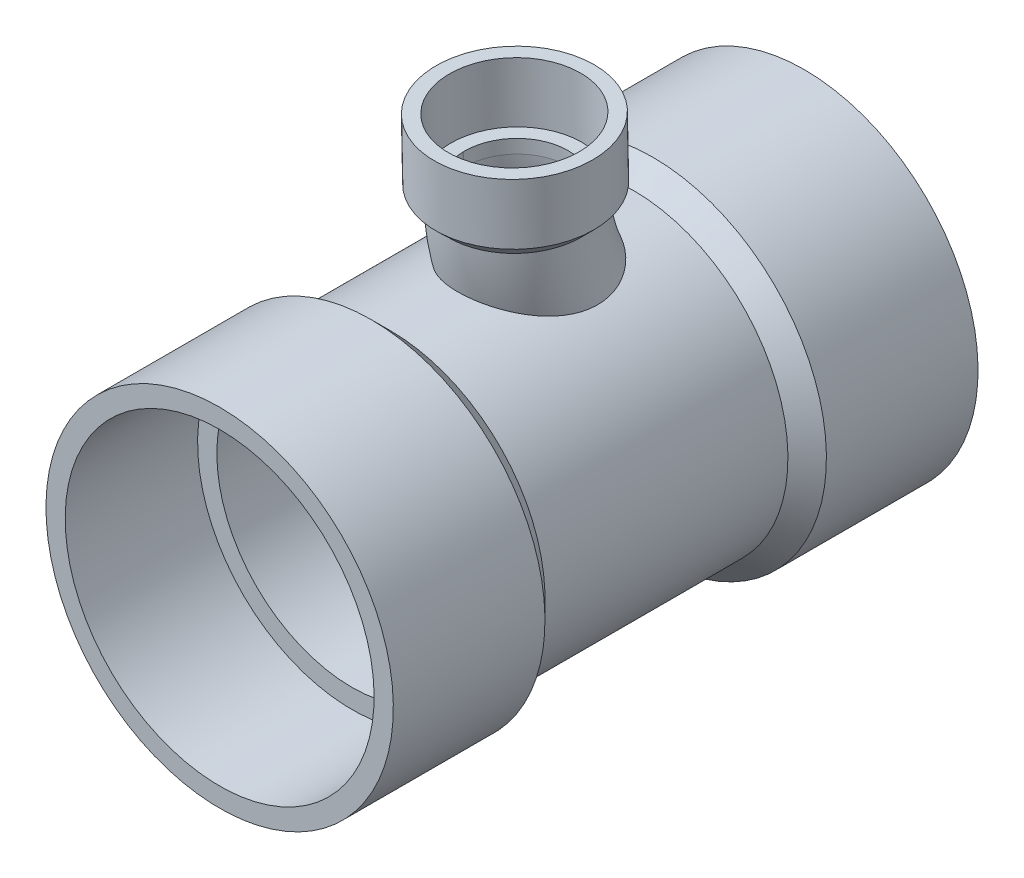
SolidWorks part; units mm, degrees
ref_plane "Front Plane" through (0, 0, 0) normal (0, 0, 1) x (1, 0, 0)
ref_plane "Top Plane" through (0, 0, 0) normal (0, 1, 0) x (1, 0, 0)
ref_plane "Right Plane" through (0, 0, 0) normal (1, 0, 0) x (0, 0, -1)
sketch "RunRoute" plane through (0, 0, 0) normal (0, 0, 1) x (1, 0, 0)
  circle A0 centre (0, 0) radius 44.45
  circle A1 centre (0, 0) radius 38.9128
  dimension "Diameter" = 88.9
  dimension "HubD" = 5.5372
sketch "Sketch2" plane through (0, 0, 0) normal (1, 0, 0) x (0, 0, -1)
  line L0 (0, 0) -> (-1.3301, 63.5) construction
  line L1 (0, 0) -> (-48.4188, 0) construction
  line L2 (0, 0) -> (43.6562, 0) construction
  arc A0 (-1.3301, 63.5) -> (43.6562, 0) centre (68.0302, 64.9529) ccw
  point P7 (43.0139, 0)
  point P8 (0, 0)
  dimension "DimensionC" = 43.6562
  dimension "DimensionB" = 92.075
  dimension "Angle" = 88.8
  dimension "DimensionA" = 63.5
ref_plane "Outlet Plane" through (0, 63.5, 1.3301) normal (0, 0.9998, 0.0209) x (1, 0, 0)
sketch "OutletRoute" plane through (0, 63.5, 1.3301) normal (0, 0.9998, 0.0209) x (1, 0, 0)
  circle A0 centre (0, 0) radius 19.05
  circle A1 centre (0, 0) radius 15.0876
  dimension "OutletHubD" = 3.9624
  dimension "OutletRoute" = 38.1
extrude "Boss-Extrude1" add sketch "RunRoute" along normal up to vertex (48.4188 mm away) and the other way up to vertex (43.6562 mm away) up to point (0, 0, 48.4188) other way up to point (0, 0, -43.6562)
sketch "Sketch6" plane through (0, 0, 0) normal (1, 0, 0) x (0, 0, -1)
  line L0 (17.7157, 63.899) -> (-20.376, 63.101) construction
  line L1 (43.6562, 44.45) -> (-48.4188, 44.45) construction
  line L2 (17.7157, 63.899) -> (17.0887, 93.8332) construction
  line L3 (-20.376, 63.101) -> (-20.9875, 92.2953) construction
  line L4 (43.6562, 44.45) -> (-48.4188, 44.45) construction
  line L6 (13.7542, 63.816) -> (-16.4144, 63.184) construction
  arc A0 (17.7157, 63.899) -> (22.0705, 44.45) centre (68.0302, 64.9529) ccw
  arc A1 (-20.376, 63.101) -> (-17.9856, 44.45) centre (68.0302, 64.9529) ccw
  arc A2 (-16.4144, 63.184) -> (-13.9067, 44.45) centre (68.0302, 64.9529) ccw
  arc A3 (13.7542, 63.816) -> (17.7628, 44.45) centre (68.0302, 64.9529) ccw
  arc A4 (-1.3301, 63.5) -> (43.6562, 0) centre (68.0302, 64.9529) ccw construction
  point P6 (0, 0)
  point P9 (0, 0)
  point P10 (24.9769, 44.45)
  point P21 (19.1248, 44.45)
  point P28 (-11.192, 44.45)
ref_plane "Plane2" through (0, 44.45, 0) normal (0, -1, 0) x (-1, 0, 0)
sweep "Sweep1" add profiles "OutletRoute" path "Sketch2"
sketch "Sketch3" plane through (0, 0, 0) normal (1, 0, 0) x (0, 0, -1)
  line L0 (43.6562, 0) -> (43.6562, -38.9128) construction
  line L1 (43.6562, -44.45) -> (81.7563, -44.45)
  line L2 (81.7563, -44.45) -> (81.7563, -49.9872)
  line L3 (81.7563, -49.9872) -> (38.1191, -49.9872)
  line L4 (38.1191, -49.9872) -> (32.5819, -44.45)
  line L5 (32.5819, -44.45) -> (32.5819, -38.9128)
  line L6 (32.5819, -38.9128) -> (43.6562, -38.9128)
  line L7 (43.6562, -38.9128) -> (43.6562, -44.45)
  line L8 (0, 0) -> (43.6562, 0) construction
  line L11 (43.6562, 0) -> (81.7562, 0) construction
  line L12 (81.7562, 0) -> (81.7563, -44.45) construction
  line L13 (-48.4188, -44.45) -> (43.6562, -44.45) construction
  line L14 (-48.4188, 0) -> (-86.5187, 0) construction
  line L15 (-86.5187, 0) -> (-86.5187, -44.45) construction
  line L16 (-86.5187, -44.45) -> (-86.5187, -49.9872)
  line L17 (-86.5187, -49.9872) -> (-42.8815, -49.9872)
  line L18 (-42.8815, -49.9872) -> (-37.3443, -44.45)
  line L19 (-37.3443, -44.45) -> (-37.3443, -38.9128)
  line L20 (-37.3443, -38.9128) -> (-48.4188, -38.9128)
  line L21 (-48.4188, -38.9128) -> (-48.4187, -44.45)
  line L22 (-48.4187, -44.45) -> (-86.5187, -44.45)
  line L25 (17.3502, 81.3449) -> (21.3118, 81.4279)
  line L26 (-1.3301, 63.5) -> (-1.6956, 80.946) construction
  line L27 (0, 0) -> (-1.3301, 63.5) construction
  line L28 (-1.6956, 80.946) -> (17.3502, 81.3449) construction
  line L29 (21.3118, 81.4279) -> (21.6805, 63.8257)
  line L30 (17.3502, 81.3449) -> (17.7157, 63.899)
  line L31 (21.6805, 63.8257) -> (17.9549, 59.9407)
  line L32 (17.9549, 59.9407) -> (13.8371, 59.8544)
  line L33 (13.8371, 59.8544) -> (13.7542, 63.816)
  line L34 (13.7542, 63.816) -> (17.7157, 63.899)
  arc A0 (17.7157, 63.899) -> (22.0705, 44.45) centre (68.0302, 64.9529) ccw construction
  point P18 (0, 0)
  dimension "HubC" = 38.1
  dimension "D1" = 5.5372
  dimension "D2" = 88.9
  dimension "D3" = 45
  dimension "D4" = 5.5372
  dimension "D5" = 45
  dimension "D6" = 5.5372
  dimension "D7" = 45
  dimension "OutletHubC" = 17.4498
  dimension "OutletHubD" = 3.9624
  dimension "D8" = 38.1
  dimension "D9" = 3.9624
extrude "Cut-Extrude1" cut sketch "RunRoute<2>" against normal through all both and the other way through all contours A1 region at (0, 0, 0)
sketch "RunRoute<2>" plane through (0, 0, 0) normal (0, 0, 1) x (1, 0, 0) same geometry as "RunRoute"
revolve "Revolve1" add sketch "Sketch3" angle 360 about L26 region at (0, 69.9322, -18.8487)
revolve "Revolve2" add sketch "Sketch3<5>" angle 360 about L14 region at (0, -46.1073, -54.5942) region at (0, -46.1073, 59.3567)
sketch "Sketch3<5>" plane through (0, 0, 0) normal (1, 0, 0) x (0, 0, -1) same geometry as "Sketch3"
ref_plane "Plane3" through (0, 0, 48.4188) normal (0, 0, 1) x (1, 0, 0)
ref_plane "Plane4" through (0, 0, -43.6562) normal (0, 0, -1) x (-1, 0, 0)
other "CPoint1" parameters "Diameter"=76.2, "StubLength"=19.05
ref_axis "Axis1" through (0, 0, 58.4188) along (0, 0, -1)
other "CPoint2" parameters "Diameter"=76.2, "StubLength"=0
ref_axis "Axis2" through (0, 0, -53.6562) along (0, 0, 1)
other "CPoint3" parameters "Diameter"=38.1, "StubLength"=152.4
ref_axis "Axis3" through (0, 73.4978, 1.5396) along (0, -0.9998, -0.0209)
other "RPoint1"
equation "\"D1@Sketch3\"=\"HubD@RunRoute\""
equation "\"D4@Sketch3\"=\"D1@Sketch3\""
equation "\"D6@Sketch3\"=\"D4@Sketch3\""
equation "\"D9@Sketch3\"=\"OutletHubD@Sketch3\""
equation "\"D8@Sketch3\"=\"OutletRoute@OutletRoute\""
equation "\"D2@Sketch3\"=\"Diameter@RunRoute\""
